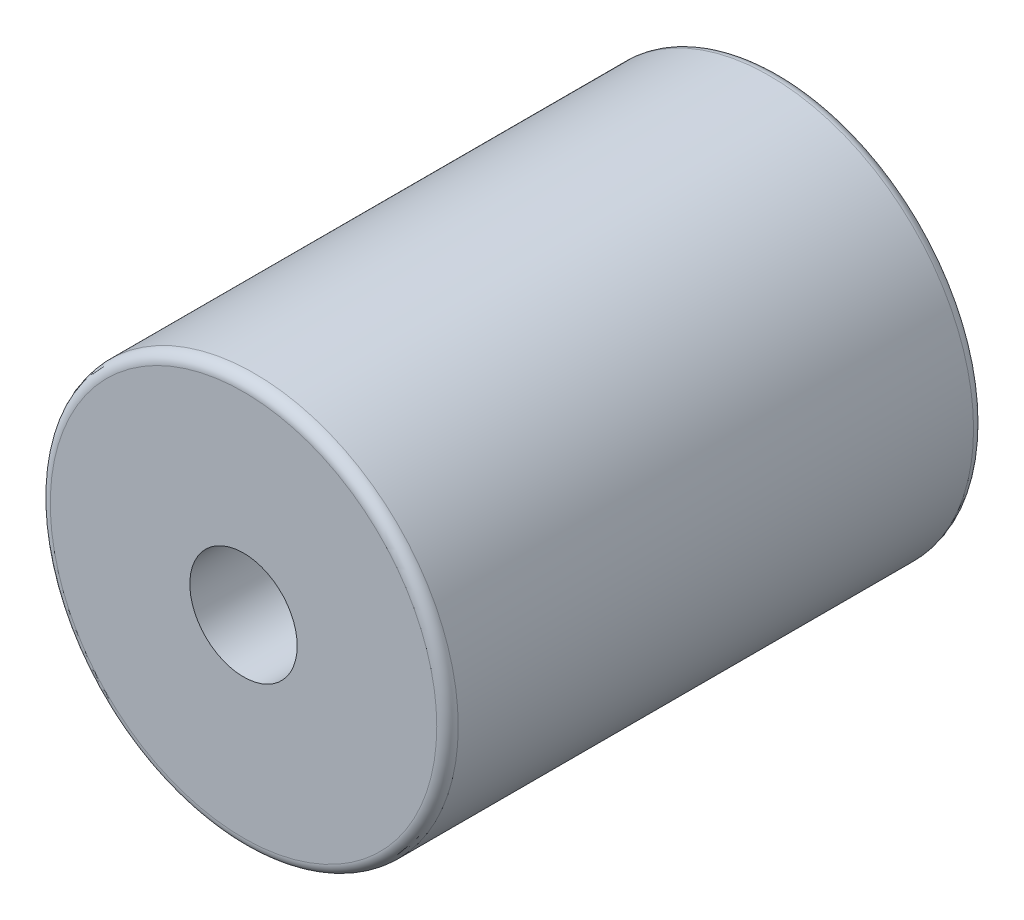
SolidWorks part; units mm, degrees
ref_plane "前视基准面" through (0, 0, 0) normal (0, 0, 1) x (1, 0, 0)
ref_plane "上视基准面" through (0, 0, 0) normal (0, 1, 0) x (1, 0, 0)
ref_plane "右视基准面" through (0, 0, 0) normal (1, 0, 0) x (0, 0, -1)
sketch "草图1" plane through (0, 0, 0) normal (0, 0, 1) x (1, 0, 0)
  circle A0 centre (0, 0) radius 9.5
extrude "凸台-拉伸1" add sketch "草图1" along normal blind 12.5 and the other way blind 12.5
sketch "草图2" plane through (0, 0, 12.5) normal (0, 0, 1) x (1, 0, 0)
  circle A0 centre (0, 0) radius 2.5
  dimension "D1" = 5
extrude "切除-拉伸1" cut sketch "草图2" against normal blind 8
sketch "草图3" plane through (0, 0, -12.5) normal (0, 0, -1) x (-1, 0, 0)
  circle A0 centre (0, 0) radius 4
  dimension "D1" = 8
extrude "切除-拉伸2" cut sketch "草图3" against normal blind 18
fillet "圆角1" radius 0.5 1 edges at (9.5, 0, -12.5)
fillet "圆角2" radius 0.5 1 edges at (9.5, 0, 12.5)
